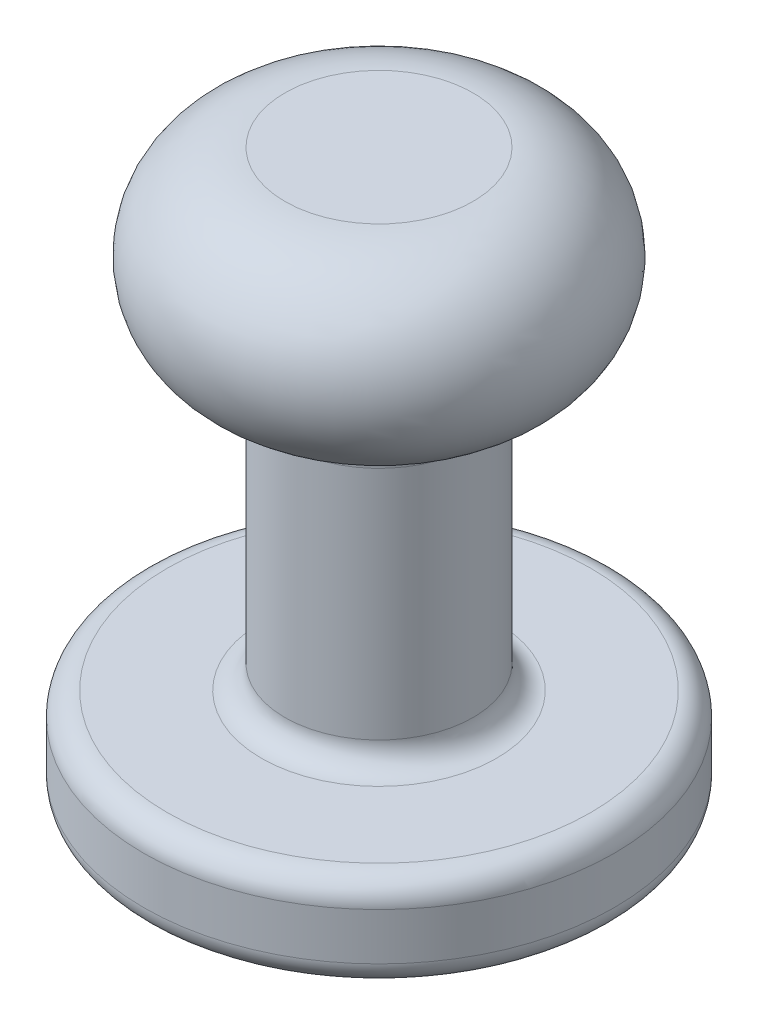
SolidWorks part; units mm, degrees
material "PE High Density"
ref_plane "Front Plane" through (0, 0, 0) normal (0, 0, 1) x (1, 0, 0)
ref_plane "Top Plane" through (0, 0, 0) normal (0, 1, 0) x (1, 0, 0)
ref_plane "Right Plane" through (0, 0, 0) normal (1, 0, 0) x (0, 0, -1)
sketch "Sketch2" plane through (0, 0, 0) normal (0, 0, 1) x (1, 0, 0)
  line L0 (0, 14.7525) -> (0, -5.2213) construction
  line L1 (0, -2) -> (4.5, -2)
  line L2 (5, -1.5) -> (5, -0.5)
  line L3 (4.5, 0) -> (2.5, 0)
  line L4 (2, 0.5) -> (2, 5.5)
  line L5 (0, 10) -> (0, -2)
  line L6 (2.5, 6) -> (2, 6)
  line L8 (0, 10) -> (2, 10)
  arc A0 (2, 10) -> (2, 6) centre (2, 8) cw
  arc A1 (2, 5.5) -> (2.5, 6) centre (2.5, 5.5) cw
  arc A2 (2.5, 0) -> (2, 0.5) centre (2.5, 0.5) cw
  arc A3 (5, -0.5) -> (4.5, 0) centre (4.5, -0.5) ccw
  arc A4 (4.5, -2) -> (5, -1.5) centre (4.5, -1.5) ccw
  point P16 (2, 6)
  point P19 (2, 0)
  point P22 (5, 0)
  point P25 (5, -2)
  dimension "D7" = 0.5
  dimension "D6" = 2
  dimension "D1" = 2
  dimension "D2" = 6
  dimension "D3" = 4
  dimension "D4" = 2
  dimension "D5" = 5
revolve "Joystick" add sketch "Sketch2" angle 360 about L0
